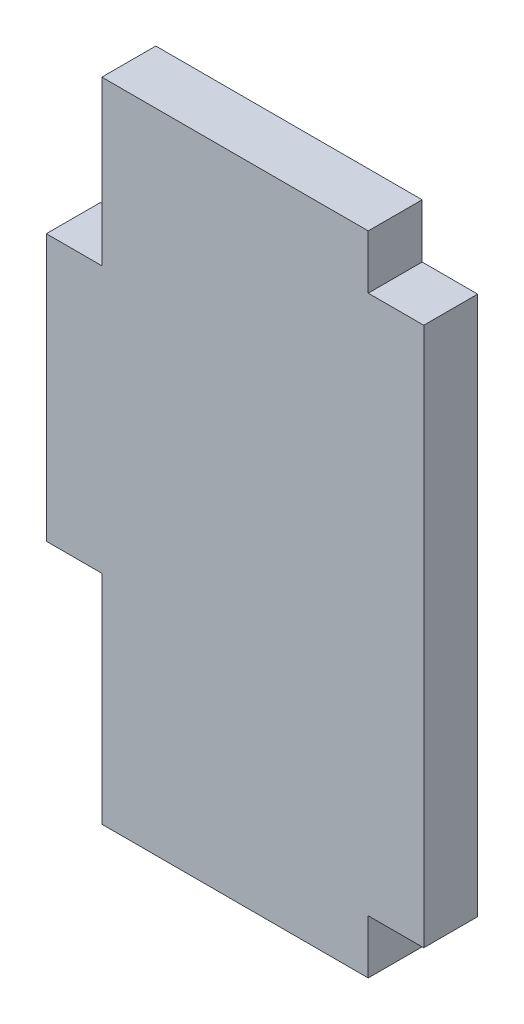
SolidWorks part; units mm, degrees
ref_plane "Front Plane" through (0, 0, 0) normal (0, 0, 1) x (1, 0, 0)
ref_plane "Top Plane" through (0, 0, 0) normal (0, 1, 0) x (1, 0, 0)
ref_plane "Right Plane" through (0, 0, 0) normal (1, 0, 0) x (0, 0, -1)
sketch "Sketch1" plane through (0, 0, 0) normal (0, 0, 1) x (1, 0, 0)
  line L0 (-5.15, 44.85) -> (0, 44.85)
  line L2 (-5.15, 44.85) -> (-5.15, 20.15)
  line L4 (29.85, 55) -> (29.85, 5)
  line L5 (0, 44.85) -> (0, 60)
  line L6 (0, 60) -> (24.7, 60)
  line L7 (24.7, 60) -> (24.7, 55)
  line L8 (24.7, 55) -> (29.85, 55)
  line L9 (-5.15, 20.15) -> (0, 20.15)
  line L10 (0, 20.15) -> (0, 0)
  line L11 (0, 0) -> (24.7, 0)
  line L12 (24.7, 0) -> (24.7, 5)
  line L13 (24.7, 5) -> (29.85, 5)
  dimension "D1" = 24.7
  dimension "D2" = 35
  dimension "D3" = 24.7
  dimension "D4" = 15.15
  dimension "D5" = 5
  dimension "D6" = 20.15
  dimension "D7" = 5
extrude "Boss-Extrude1" add sketch "Sketch1" along normal blind 5
